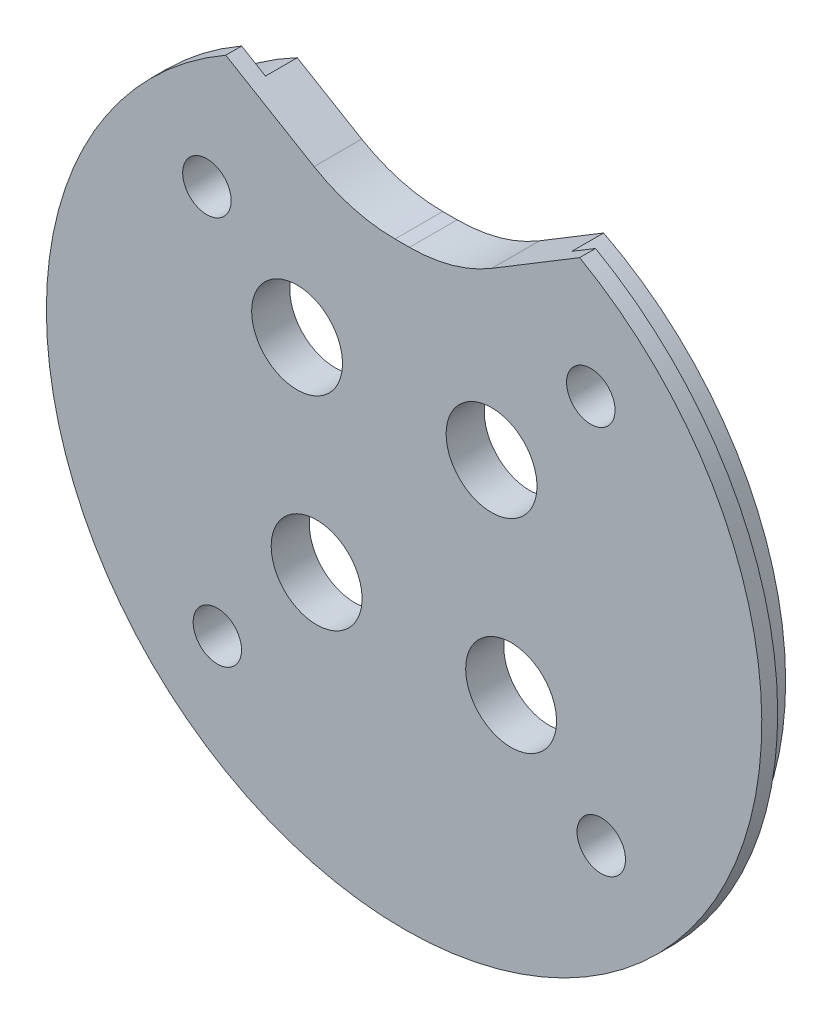
SolidWorks part; units mm, degrees
ref_plane "Front Plane" through (0, 0, 0) normal (0, 0, 1) x (1, 0, 0)
ref_plane "Top Plane" through (0, 0, 0) normal (0, 1, 0) x (1, 0, 0)
ref_plane "Right Plane" through (0, 0, 0) normal (1, 0, 0) x (0, 0, -1)
sketch "Sketch1" plane through (0, 0, 0) normal (0, 0, 1) x (1, 0, 0)
  circle A0 centre (0, 0) radius 21
  dimension "D1" = 42
extrude "Boss-Extrude1" add sketch "Sketch1" along normal blind 2
sketch "Sketch2" plane through (0, 0, 2) normal (0, 0, 1) x (1, 0, 0)
  circle A0 centre (0, 0) radius 22.5
  dimension "D1" = 45
extrude "Boss-Extrude2" add sketch "Sketch2" along normal blind 1
sketch "Sketch3" plane through (0, 0, 0) normal (0, 0, -1) x (-1, 0, 0)
  line L12 (14.6571, 13.7051) -> (14.4825, 13.8895)
  line L13 (8.0604, 2.3857) -> (14.5153, 8.4984)
  line L14 (14.0313, -9.2759) -> (7.9186, -2.8209)
  line L15 (13.7051, -14.6571) -> (13.8895, -14.4825)
  line L16 (2.3857, -8.0604) -> (8.4984, -14.5153)
  line L17 (-9.2759, -14.0313) -> (-2.8209, -7.9186)
  line L18 (-14.6571, -13.7051) -> (-14.4825, -13.8895)
  line L19 (-8.0604, -2.3857) -> (-14.5153, -8.4984)
  line L20 (-14.0313, 9.2759) -> (-7.9186, 2.8209)
  line L21 (-13.7051, 14.6571) -> (-13.8895, 14.4825)
  line L22 (-2.3857, 8.0604) -> (-8.4984, 14.5153)
  line L23 (9.2759, 14.0313) -> (2.8209, 7.9186)
  line L24 (14.6571, 13.7051) -> (14.4825, 13.8895)
  line L25 (8.0604, 2.3857) -> (14.5153, 8.4984)
  line L26 (14.0313, -9.2759) -> (7.9186, -2.8209)
  line L27 (13.7051, -14.6571) -> (13.8895, -14.4825)
  line L28 (2.3857, -8.0604) -> (8.4984, -14.5153)
  line L29 (-9.2759, -14.0313) -> (-2.8209, -7.9186)
  line L30 (-14.6571, -13.7051) -> (-14.4825, -13.8895)
  line L31 (-8.0604, -2.3857) -> (-14.5153, -8.4984)
  line L32 (-14.0313, 9.2759) -> (-7.9186, 2.8209)
  line L33 (-13.7051, 14.6571) -> (-13.8895, 14.4825)
  line L34 (-2.3857, 8.0604) -> (-8.4984, 14.5153)
  line L35 (9.2759, 14.0313) -> (2.8209, 7.9186)
  arc A12 (14.4825, 13.8895) -> (9.2759, 14.0313) centre (11.8083, 11.3571) ccw
  arc A13 (14.5153, 8.4984) -> (14.6571, 13.7051) centre (11.9829, 11.1726) ccw
  arc A14 (8.0604, 2.3857) -> (7.9186, -2.8209) centre (10.5928, -0.2885) ccw
  arc A15 (13.8895, -14.4825) -> (14.0313, -9.2759) centre (11.3571, -11.8083) ccw
  arc A16 (8.4984, -14.5153) -> (13.7051, -14.6571) centre (11.1726, -11.9829) ccw
  arc A17 (2.3857, -8.0604) -> (-2.8209, -7.9186) centre (-0.2885, -10.5928) ccw
  arc A18 (-14.4825, -13.8895) -> (-9.2759, -14.0313) centre (-11.8083, -11.3571) ccw
  arc A19 (-14.5153, -8.4984) -> (-14.6571, -13.7051) centre (-11.9829, -11.1726) ccw
  arc A20 (-8.0604, -2.3857) -> (-7.9186, 2.8209) centre (-10.5928, 0.2885) ccw
  arc A21 (-13.8895, 14.4825) -> (-14.0313, 9.2759) centre (-11.3571, 11.8083) ccw
  arc A22 (-8.4984, 14.5153) -> (-13.7051, 14.6571) centre (-11.1726, 11.9829) ccw
  arc A23 (-2.3857, 8.0604) -> (2.8209, 7.9186) centre (0.2885, 10.5928) ccw
  arc A24 (14.4825, 13.8895) -> (9.2759, 14.0313) centre (11.8083, 11.3571) ccw
  arc A25 (14.5153, 8.4984) -> (14.6571, 13.7051) centre (11.9829, 11.1726) ccw
  arc A26 (8.0604, 2.3857) -> (7.9186, -2.8209) centre (10.5928, -0.2885) ccw
  arc A27 (13.8895, -14.4825) -> (14.0313, -9.2759) centre (11.3571, -11.8083) ccw
  arc A28 (8.4984, -14.5153) -> (13.7051, -14.6571) centre (11.1726, -11.9829) ccw
  arc A29 (2.3857, -8.0604) -> (-2.8209, -7.9186) centre (-0.2885, -10.5928) ccw
  arc A30 (-14.4825, -13.8895) -> (-9.2759, -14.0313) centre (-11.8083, -11.3571) ccw
  arc A31 (-14.5153, -8.4984) -> (-14.6571, -13.7051) centre (-11.9829, -11.1726) ccw
  arc A32 (-8.0604, -2.3857) -> (-7.9186, 2.8209) centre (-10.5928, 0.2885) ccw
  arc A33 (-13.8895, 14.4825) -> (-14.0313, 9.2759) centre (-11.3571, 11.8083) ccw
  arc A34 (-8.4984, 14.5153) -> (-13.7051, 14.6571) centre (-11.1726, 11.9829) ccw
  arc A35 (-2.3857, 8.0604) -> (2.8209, 7.9186) centre (0.2885, 10.5928) ccw
  dimension "D1" = 0
extrude "Cut-Extrude1" cut sketch "Sketch3" against normal blind 0.6
sketch "Sketch4" plane through (0, 0, 0) normal (0, 0, -1) x (-1, 0, 0)
  line L0 (-11.0406, 19.605) -> (-5.5185, 16.2613)
  line L1 (-0.339, 14.8154) -> (0.5675, 14.8154)
  line L2 (5.6655, 16.2124) -> (11.2191, 19.5034)
  line L3 (0, 17.764) -> (0, -3.3693) construction
  arc A0 (-11.0406, 19.605) -> (11.2191, 19.5034) centre (0, 0) cw
  circle A1 centre (0, 0) radius 22.5 construction
  arc A2 (0.5675, 14.8154) -> (5.6655, 16.2124) centre (0.5675, 24.8154) ccw
  arc A3 (-5.5185, 16.2613) -> (-0.339, 14.8154) centre (-0.339, 24.8154) ccw
  circle A4 centre (12.4028, 11.7451) radius 1.524 construction
  circle A5 centre (12.4028, 11.7451) radius 1.524
  circle A6 centre (11.7451, -12.4028) radius 1.524 construction
  circle A7 centre (11.7451, -12.4028) radius 1.524
  circle A8 centre (-12.4028, -11.7451) radius 1.524 construction
  circle A9 centre (-12.4028, -11.7451) radius 1.524
  circle A10 centre (-11.7451, 12.4028) radius 1.524 construction
  circle A11 centre (-11.7451, 12.4028) radius 1.524
  circle A12 centre (6.7316, 6.3747) radius 2.8575 construction
  circle A13 centre (-5.5014, 5.8095) radius 2.8575
  circle A14 centre (-5.5014, 5.8095) radius 2.8575
  circle A15 centre (6.7316, 6.3747) radius 2.8575
  circle A16 centre (5.5014, -5.8095) radius 2.8575 construction
  circle A17 centre (5.5014, -5.8095) radius 2.8575
  circle A19 centre (-6.7316, -6.3747) radius 2.8575
  circle A20 centre (-6.7316, -6.3747) radius 2.8575
  spline S0 degree 3 poles (-1.2595, -31.5089) (1.4307, -31.4385) (2.3223, -31.3719) (4.0964, -31.1543) (4.9817, -31.0024) (7.6006, -30.4232) (9.2857, -29.877) (11.7243, -28.8244) (12.5223, -28.4346) (13.6966, -27.7899) (14.0851, -27.5644) (14.8475, -27.0972) (15.2218, -26.8553) (17.0594, -25.6048) (18.4217, -24.4743) (19.987, -22.895) (20.2931, -22.5708) (20.8913, -21.9054) (21.1832, -21.564) (22.0285, -20.5252) (22.5543, -19.8093) (23.5318, -18.3317) (23.9834, -17.57) (24.8107, -15.9995) (25.1869, -15.189) (26.1919, -12.6944) (26.6823, -10.9905) (27.1519, -8.3743) (27.2641, -7.4921) (27.3629, -6.1531) (27.3841, -5.7041) (27.4027, -4.8115) (27.4002, -4.3666) (27.3302, -2.1489) (27.0921, -0.3963) (26.4592, 2.1998) (26.2004, 3.0634) (25.6017, 4.7408) (25.261, 5.5585) (24.1191, 7.9511) (23.1988, 9.4678) (21.0391, 12.3316) (19.8362, 13.6319) (17.8577, 15.3962) (17.1691, 15.9532) (15.7333, 17.0045) (14.9822, 17.5009) (12.6845, 18.8669) (11.0855, 19.6224) (8.5884, 20.5279) (7.7396, 20.7917) (6.441, 21.1288) (6.004, 21.2314) (5.1308, 21.4147) (4.6934, 21.4959) (2.503, 21.8499) (0.739, 21.9685) (-1.4806, 21.9096) (-1.9253, 21.8874) (-2.8161, 21.8219) (-3.2632, 21.7785) (-4.5938, 21.6176) (-5.47, 21.4697) (-8.0665, 20.9065) (-9.7551, 20.3728) (-11.8109, 19.5003) (-12.2201, 19.315) (-13.0254, 18.9272) (-13.4221, 18.7243) (-14.5946, 18.0894) (-15.3529, 17.6309) (-16.8227, 16.6439) (-17.5342, 16.1153) (-18.5653, 15.2681) (-18.903, 14.9766) (-19.5659, 14.3749) (-19.8907, 14.065) (-21.4668, 12.4855) (-22.5886, 11.1143) (-23.8153, 9.2644) (-24.0518, 8.8875) (-24.5066, 8.1199) (-24.7256, 7.7281) (-25.3504, 6.5385) (-25.7226, 5.7303) (-26.71, 3.2618) (-27.1977, 1.5581) (-27.5831, -0.6479) (-27.6487, -1.0921) (-27.7559, -1.9778) (-27.7978, -2.4205) (-27.8885, -3.7481) (-27.9024, -4.6325) (-27.8384, -6.4) (-27.7607, -7.283) (-27.5124, -9.0479) (-27.3403, -9.9328) (-26.6957, -12.5238) (-26.0961, -14.1862) (-24.9482, -16.5848) (-24.5231, -17.3701) (-23.592, -18.9016) (-23.0923, -19.6378) (-21.4953, -21.7615) (-20.3016, -23.0654) (-18.3164, -24.8526) (-17.6188, -25.4221) (-16.1866, -26.4815) (-15.4495, -26.9742) (-13.1769, -28.3441) (-11.5806, -29.1144) (-9.0583, -30.0447) (-8.2076, -30.3127) (-6.4956, -30.7652) (-5.6329, -30.9501) (-3.0247, -31.3826) (-1.2595, -31.5089) (1.4307, -31.4385) (2.3223, -31.3719) knots -0.03125 -0.03125 0 0 0.015625 0.015625 0.03125 0.03125 0.0625 0.0625 0.078125 0.078125 0.085938 0.085938 0.09375 0.09375 0.125 0.125 0.132813 0.132813 0.140625 0.140625 0.15625 0.15625 0.171875 0.171875 0.1875 0.1875 0.21875 0.21875 0.234375 0.234375 0.242188 0.242188 0.25 0.25 0.28125 0.28125 0.296875 0.296875 0.3125 0.3125 0.34375 0.34375 0.375 0.375 0.390625 0.390625 0.40625 0.40625 0.4375 0.4375 0.453125 0.453125 0.460938 0.460938 0.46875 0.46875 0.5 0.5 0.507813 0.507813 0.515625 0.515625 0.53125 0.53125 0.5625 0.5625 0.570313 0.570313 0.578125 0.578125 0.59375 0.59375 0.609375 0.609375 0.617188 0.617188 0.625 0.625 0.65625 0.65625 0.664063 0.664063 0.671875 0.671875 0.6875 0.6875 0.71875 0.71875 0.726563 0.726563 0.734375 0.734375 0.75 0.75 0.765625 0.765625 0.78125 0.78125 0.8125 0.8125 0.828125 0.828125 0.84375 0.84375 0.875 0.875 0.890625 0.890625 0.90625 0.90625 0.9375 0.9375 0.953125 0.953125 0.96875 0.96875 1 1 1.015625 1.015625 1.03125 only from (0.534, -31.4619) to (0.534, -31.4619) construction
  dimension "D1" = 10
  dimension "D2" = 0
  dimension "D3" = 0
extrude "Cut-Extrude2" cut sketch "Sketch4" against normal up to next
